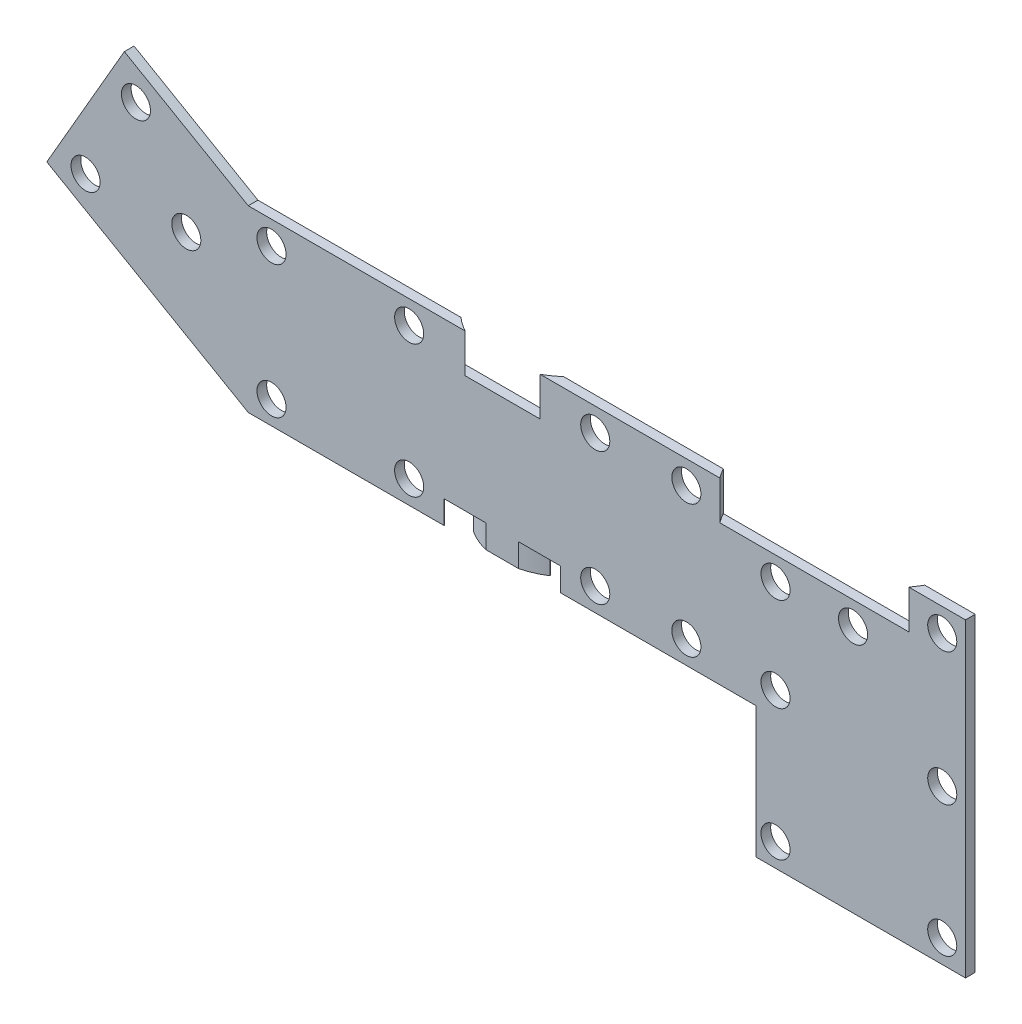
SolidWorks part; units mm, degrees
material "1023 Carbon Steel Sheet (SS)"
ref_plane "Front Plane" through (0, 0, 0) normal (0, 0, 1) x (1, 0, 0)
ref_plane "Top Plane" through (0, 0, 0) normal (0, 1, 0) x (1, 0, 0)
ref_plane "Right Plane" through (0, 0, 0) normal (1, 0, 0) x (0, 0, -1)
sketch "Sketch1" plane through (0, 0, 0) normal (0, 0, 1) x (1, 0, 0)
  line L0 (0, 0) -> (-40.5911, 23.4353)
  line L1 (-40.5911, 23.4353) -> (-65.9911, -20.5588)
  line L2 (-65.9911, -20.5588) -> (0, -58.6588)
  line L3 (0, -58.6588) -> (64.135, -58.6588)
  line L4 (64.135, -58.6588) -> (64.135, -51.0388)
  line L5 (64.135, -51.0388) -> (70.612, -51.0388)
  line L6 (70.612, -51.0388) -> (70.612, -58.6588)
  line L7 (70.612, -58.6588) -> (95.758, -58.6588)
  line L8 (95.758, -58.6588) -> (95.758, -51.0388)
  line L9 (95.758, -51.0388) -> (102.235, -51.0388)
  line L10 (102.235, -51.0388) -> (102.235, -58.6588)
  line L11 (102.235, -58.6588) -> (166.37, -58.6588)
  line L12 (166.37, -58.6588) -> (166.37, -101.6)
  line L13 (166.37, -101.6) -> (234.95, -101.6)
  line L14 (234.95, -101.6) -> (234.95, 0)
  line L23 (234.95, 0) -> (0, 0)
  circle A1 centre (-20.2956, -17.6117) radius 4.7625
  circle A2 centre (-53.2911, -17.6117) radius 4.7625
  circle A3 centre (-36.7934, 10.9633) radius 4.7625
  circle A4 centre (-36.7934, -8.0867) radius 19.05 construction
  circle A5 centre (7.62, -51.0388) radius 4.7625
  circle A6 centre (7.62, -7.62) radius 4.7625
  circle A7 centre (52.705, -7.62) radius 4.7625
  circle A8 centre (113.665, -7.62) radius 4.7625
  circle A9 centre (143.51, -7.62) radius 4.7625
  circle A10 centre (113.665, -51.0388) radius 4.7625
  circle A11 centre (52.705, -51.0388) radius 4.7625
  circle A12 centre (143.51, -51.0388) radius 4.7625
  circle A13 centre (172.72, -20.32) radius 4.7625
  circle A14 centre (198.12, -20.32) radius 4.7625
  circle A15 centre (227.33, -7.62) radius 4.7625
  circle A16 centre (227.33, -93.98) radius 4.7625
  circle A17 centre (172.72, -93.98) radius 4.7625
  circle A18 centre (227.33, -51.0388) radius 4.7625
  circle A19 centre (172.72, -51.0388) radius 4.7625
  point P3 (-36.7934, -8.0867)
  point P18 (232.0925, 0)
  point P19 (0, 0)
  point P28 (-53.2911, 1.4383)
  point P33 (83.185, -58.6588)
  dimension "D18" = 9.525
  dimension "D21" = 3
  dimension "D16" = 38.1
  dimension "D17" = 7.62
  dimension "D1" = 30
  dimension "D2" = 76.2
  dimension "D3" = 50.8
  dimension "D4" = 83.185
  dimension "D5" = 234.95
  dimension "D6" = 38.1
  dimension "D7" = 29.845
  dimension "D8" = 25.146
  dimension "D9" = 166.37
  dimension "D10" = 7.62
  dimension "D11" = 20.32
  dimension "D12" = 29.21
  dimension "D13" = 101.6
  dimension "D14" = 25.4
  dimension "D15" = 7.62
  dimension "D19" = 19.05
  dimension "D20" = 25.4
  dimension "D22" = 7.62
  dimension "D23" = 7.62
  dimension "D24" = 30.48
  dimension "D25" = 30.48
  dimension "D30" = 7.62
  dimension "D32" = 7.62
extrude "Boss-Extrude1" add sketch "Sketch1" along normal blind 3.175
sketch "Sketch2" plane through (0, -58.6588, 0) normal (0, -1, 0) x (1, 0, 0)
  line L0 (70.612, 0) -> (95.758, 0) construction
  line L3 (83.185, 0) -> (83.185, -19.05) construction
  circle A0 centre (83.185, -19.05) radius 22.86
  circle A1 centre (83.185, -19.05) radius 29.21
  point P2 (0, 0)
  point P3 (0, 0)
  point P4 (0, 0)
  dimension "D2" = 45.72
  dimension "D3" = 6.35
  dimension "D1" = 19.05
extrude "Cut-Extrude1" cut sketch "Sketch2" against normal blind 7.62
sketch "Sketch5" plane through (0, 0, 0) normal (0, 1, 0) x (1, 0, 0)
  line L0 (234.95, -1.5875) -> (185.42, -1.5875) construction
  line L1 (234.95, -3.175) -> (234.95, 0) construction
  line L2 (185.42, 0) -> (185.42, 19.05) construction
  line L5 (0, -1.5875) -> (83.312, -1.5875) construction
  line L6 (0, -3.175) -> (0, 0) construction
  line L7 (234.95, 0) -> (0, 0) construction
  circle A0 centre (185.42, 19.05) radius 38.1
  circle A1 centre (83.312, 19.05) radius 25.4
  point P5 (0, 0)
  point P7 (0, 0)
  point P17 (0, 0)
  point P18 (0, 0)
  point P19 (185.42, 21.2829)
  dimension "D3" = 76.2
  dimension "D5" = 50.8
  dimension "D1" = 49.53
  dimension "D2" = 19.05
  dimension "D4" = 83.312
extrude "Cut-Extrude5" cut sketch "Sketch5" against normal blind 12.7
